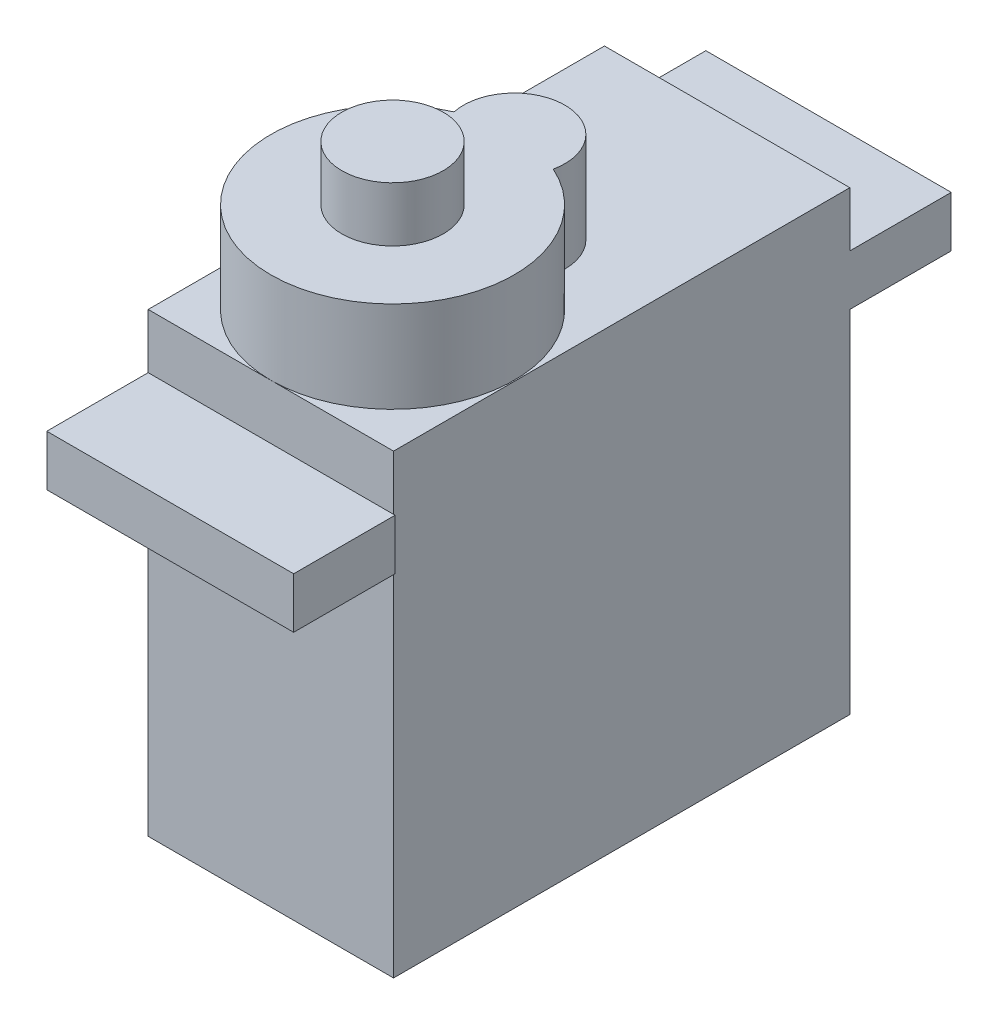
SolidWorks part; units mm, degrees
material "Custom Plastic"
ref_plane "Front Plane" through (0, 0, 0) normal (0, 0, 1) x (1, 0, 0)
ref_plane "Top Plane" through (0, 0, 0) normal (0, 1, 0) x (1, 0, 0)
ref_plane "Right Plane" through (0, 0, 0) normal (1, 0, 0) x (0, 0, -1)
sketch "Sketch1" plane through (0, 0, 0) normal (0, 1, 0) x (1, 0, 0)
  line L1 (-6.05, 11.25) -> (6.05, 11.25)
  line L2 (-6.05, 11.25) -> (-6.05, -11.25)
  line L3 (-6.05, -11.25) -> (6.05, -11.25)
  line L4 (6.05, 11.25) -> (6.05, -11.25)
  line L5 (-6.05, 11.25) -> (6.05, -11.25) construction
  line L6 (-6.05, -11.25) -> (6.05, 11.25) construction
  point P0 (0, 0)
  dimension "D1" = 22.5
  dimension "D2" = 12.1
extrude "Boss-Extrude1" add sketch "Sketch1" along normal blind 22.5
sketch "Sketch2" plane through (0, 22.5, 0) normal (0, 1, 0) x (1, 0, 0)
  line L0 (-0.075, 3.625) -> (6.05, 3.625) construction
  line L2 (6.05, -11.25) -> (6.05, 11.25) construction
  line L3 (0, -11.25) -> (0, -5.25) construction
  line L4 (-6.05, -11.25) -> (6.05, -11.25) construction
  line L6 (0, -5.25) -> (0, 0.75) construction
  arc A4 (-2.4451, 0.2292) -> (2.4451, 0.2292) centre (0, -5.25) ccw
  arc A5 (2.4451, 0.2292) -> (-2.4451, 0.2292) centre (0, 0.75) ccw
  circle A6 centre (0, -5.25) radius 2.5
  dimension "D1" = 6
  dimension "D3" = 5
  dimension "D4" = 5
  dimension "D2" = 6
extrude "Boss-Extrude2" add sketch "Sketch2" along normal blind 4.5 contours A4 A5
extrude "Boss-Extrude3" add sketch "Sketch2<3>" along normal blind 7.2 contours A6
sketch "Sketch2<3>" plane through (0, 22.5, 0) normal (0, 1, 0) x (1, 0, 0) same geometry as "Sketch2"
sketch "Sketch9" plane through (0, 0, 11.25) normal (0, 0, 1) x (1, 0, 0)
  line L0 (0, 0) -> (0, 10.3008) construction
  line L6 (-6.05, 0) -> (6.05, 0) construction
  circle A0 centre (0, 1.27) radius 1.27
  circle A3 centre (-2.6, 1.27) radius 1.27
  circle A4 centre (2.6, 1.27) radius 1.27
  point P3 (0, 1.27)
  dimension "D3" = 2.54
  dimension "D2" = 2.54
  dimension "D4" = 2.54
  dimension "D1" = 1.27
  dimension "D5" = 2.6
  dimension "D6" = 2.6
extrude "Boss-Extrude7" add sketch "Sketch9" along normal blind 3 contours L0 A0 | A0 L0 | A4 | A3 region at (-0.539, 1.27, 11.25) region at (0.539, 1.27, 11.25) region at (2.6, 1.27, 11.25)
sketch "Sketch12" plane through (0, 0, 0) normal (0, -1, 0) x (1, 0, 0)
  line L0 (-6.05, 11.25) -> (-6.05, 16.25)
  line L1 (-6.05, 16.25) -> (6.125, 16.25)
  line L2 (6.125, 16.25) -> (6.125, 11.25)
  line L3 (2.6, 11.25) -> (6.05, 11.25) construction
  line L4 (6.125, 11.25) -> (-6.05, 11.25)
  line L5 (-6.05, -11.25) -> (6.05, -11.25)
  line L6 (6.05, -11.25) -> (6.05, -16.25)
  line L7 (6.05, -16.25) -> (-6.05, -16.25)
  line L8 (-6.05, -16.25) -> (-6.05, -11.25)
  dimension "D1" = 5
  dimension "D2" = 5
extrude "Boss-Extrude8" add sketch "Sketch12" against normal blind 19.8
extrude "Cut-Extrude1" cut sketch "Sketch12<2>" against normal blind 17.3
sketch "Sketch12<2>" plane through (0, 0, 0) normal (0, -1, 0) x (1, 0, 0) same geometry as "Sketch12"
